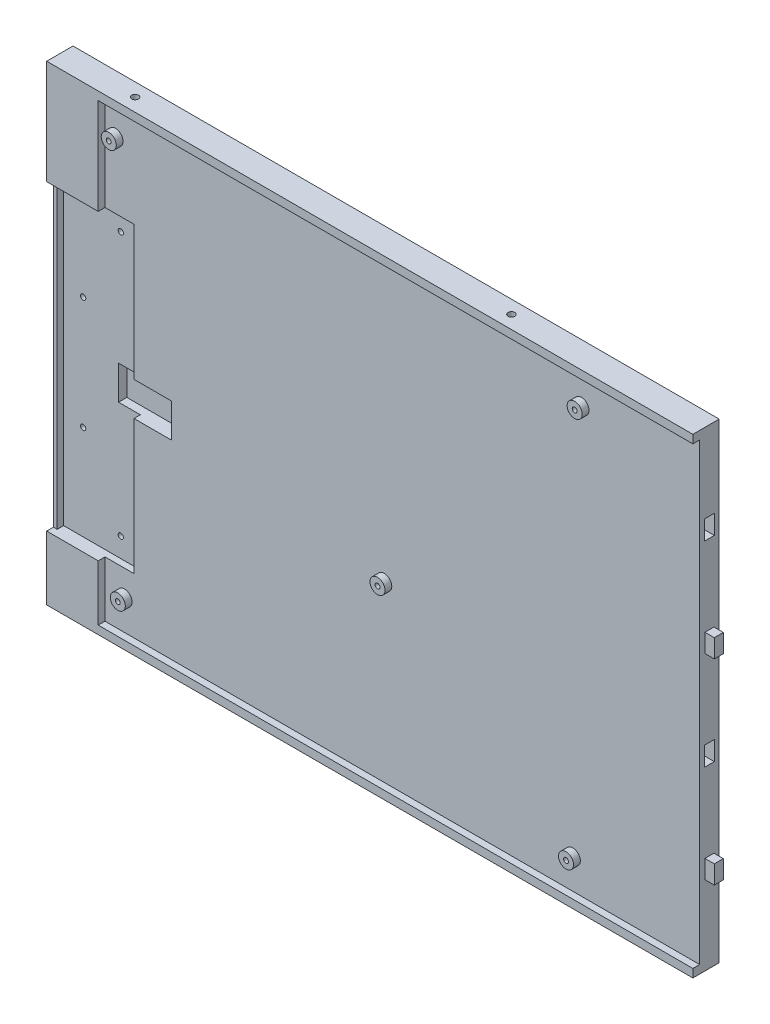
SolidWorks part; units mm, degrees
ref_plane "前视基准面" through (0, 0, 0) normal (0, 0, 1) x (1, 0, 0)
ref_plane "上视基准面" through (0, 0, 0) normal (0, 1, 0) x (1, 0, 0)
ref_plane "右视基准面" through (0, 0, 0) normal (1, 0, 0) x (0, 0, -1)
other "Configuration Table"
sketch "草图1" plane through (0, 0, 0) normal (0, 0, 1) x (1, 0, 0)
  line L1 (0, 0) -> (348.235, 0)
  line L2 (0, 0) -> (0, -124.714)
  line L3 (0, -124.714) -> (348.235, -124.714)
  line L4 (348.235, 0) -> (348.235, -124.714)
  dimension "D1" = 348.235
  dimension "D2" = 124.714
extrude "凸台-拉伸1" add sketch "草图1" along normal blind 7
sketch "草图2" plane through (0, 0, 7) normal (0, 0, 1) x (1, 0, 0)
  line L0 (348.235, 0) -> (0, 0) construction
  line L1 (2, -2) -> (346.235, -2)
  line L2 (2, -2) -> (2, -122.714)
  line L3 (2, -122.714) -> (346.235, -122.714)
  line L4 (346.235, -2) -> (346.235, -122.714)
  line L5 (348.235, -124.714) -> (348.235, 0) construction
  line L6 (0, -124.714) -> (348.235, -124.714) construction
  line L7 (0, 0) -> (0, -124.714) construction
  dimension "D1" = 2
  dimension "D2" = 2
  dimension "D3" = 2
  dimension "D4" = 2
extrude "切除-拉伸1" cut sketch "草图2" against normal blind 1.8
sketch "草图3" plane through (0, 0, 5.2) normal (0, 0, 1) x (1, 0, 0)
  circle A0 centre (4.8, -9.9) radius 2
  circle A1 centre (4.8, -9.9) radius 0.65
  circle A2 centre (7.2, -114.7) radius 2
  circle A3 centre (7.2, -114.7) radius 0.65
  circle A4 centre (76.2, -76.6) radius 2
  circle A5 centre (76.2, -76.6) radius 0.65
  circle A6 centre (128.6, -9.9) radius 2
  circle A7 centre (128.6, -9.9) radius 0.65
  circle A8 centre (126.3, -114.7) radius 2
  circle A9 centre (126.3, -114.7) radius 0.65
  circle A10 centre (185.8, -57.5) radius 2
  circle A11 centre (185.8, -57.5) radius 0.65
  circle A12 centre (252.5, -9.9) radius 2
  circle A13 centre (252.5, -9.9) radius 0.65
  circle A14 centre (245.3, -114.7) radius 2
  circle A15 centre (245.3, -114.7) radius 0.65
  circle A16 centre (333.4, -9.9) radius 2
  circle A17 centre (333.4, -9.9) radius 0.65
  circle A18 centre (333.4, -114.7) radius 2
  circle A19 centre (333.4, -114.7) radius 0.65
  circle A20 centre (266.8, -57.5) radius 2
  circle A21 centre (266.8, -57.5) radius 0.65
  dimension "D1" = 4
  dimension "D2" = 1.3
extrude "凸台-拉伸2" add sketch "草图3" along normal up to surface (1.8 mm away) up to face at (174.1175, -62.357, 7)
sketch "草图4" plane through (0, 0, 5.2) normal (0, 0, 1) x (1, 0, 0)
  line L0 (0, 0) -> (0, -124.714) construction
  line L1 (0, -27.514) -> (9.7, -27.514)
  line L2 (0, -27.514) -> (0, -107.914)
  line L3 (0, -107.914) -> (9.7, -107.914)
  line L4 (9.7, -27.514) -> (9.7, -107.914)
  line L5 (0, -124.714) -> (348.235, -124.714) construction
  dimension "D1" = 80.4
  dimension "D2" = 9.7
  dimension "D3" = 16.8
extrude "切除-拉伸2" cut sketch "草图4" against normal blind 1.7 and the other way through all contours L4 L3 L2 L1
sketch "草图6" plane through (0, 0, 5.2) normal (0, 0, 1) x (1, 0, 0)
  line L5 (3.9, -67.714) -> (9.7, -67.714) construction
  line L6 (3.9, -63.214) -> (19.7, -63.214)
  line L7 (3.9, -63.214) -> (3.9, -72.214)
  line L8 (3.9, -72.214) -> (19.7, -72.214)
  line L9 (19.7, -63.214) -> (19.7, -72.214)
  line L10 (9.7, -27.514) -> (9.7, -107.914) construction
  dimension "D1" = 9
  dimension "D2" = 5.8
  dimension "D3" = 10
extrude "切除-拉伸3" cut sketch "草图6" against normal offset from surface (3.9 mm away) 1.3 up to face at (174.1175, -62.357, 0)
sketch "草图7" plane through (0, 0, 0) normal (-1, 0, 0) x (0, 0, 1)
  line L1 (0, 0) -> (7, 0)
  line L2 (0, 0) -> (0, -27.514)
  line L3 (0, -27.514) -> (7, -27.514)
  line L4 (7, 0) -> (7, -27.514)
  line L5 (7, -107.914) -> (0, -107.914)
  line L6 (7, -107.914) -> (7, -124.714)
  line L7 (7, -124.714) -> (0, -124.714)
  line L8 (0, -107.914) -> (0, -124.714)
  line L9 (0, -107.914) -> (3.5, -107.914)
  line L10 (0, -107.914) -> (0, -27.514)
  line L11 (0, -27.514) -> (3.5, -27.514)
  line L12 (3.5, -107.914) -> (3.5, -27.514)
  line M1 (3.5, -107.914) -> (3.5, -27.514)
  line M2 (3.5, -27.514) -> (7, -27.514)
  line M3 (7, -27.514) -> (7, 0)
  line M4 (7, 0) -> (0, 0)
  line M5 (0, 0) -> (0, -124.714)
  line M6 (0, -124.714) -> (7, -124.714)
  line M7 (7, -124.714) -> (7, -107.914)
  line M8 (7, -107.914) -> (3.5, -107.914)
extrude "凸台-拉伸3" add sketch "草图7" along normal blind 11.7 contours L5 M8 M5 M6 M7 | L5 L3 M1 M5 | L3 M5 M2 M3 M4 region at (0, -13.757, 3.5) region at (0, -67.714, 1.75) region at (0, -116.314, 3.5)
sketch "草图8" plane through (0, 0, 3.5) normal (0, 0, 1) x (1, 0, 0)
  circle A0 centre (-5.5, -82.714) radius 0.7
  circle A1 centre (4.5, -102.714) radius 0.7
  circle A2 centre (-5.5, -52.714) radius 0.7
  circle A3 centre (4.5, -32.714) radius 0.7
  dimension "D1" = 1.4
extrude "切除-拉伸4" cut sketch "草图8" against normal blind 3
sketch "草图9" plane through (0, 0, 3.5) normal (0, 0, 1) x (1, 0, 0)
  line L0 (-11.7, -107.914) -> (2, -107.914) construction
  line L1 (-11.7, -27.514) -> (-10.7, -27.514)
  line L2 (-11.7, -27.514) -> (-11.7, -107.914)
  line L3 (-11.7, -107.914) -> (-10.7, -107.914)
  line L4 (-10.7, -27.514) -> (-10.7, -107.914)
  dimension "D1" = 1
extrude "凸台-拉伸4" add sketch "草图9" along normal up to surface (1.7 mm away) up to face at (64.8892, -65.9283, 5.2)
sketch "草图10" plane through (0, 0, 5.2) normal (0, 0, 1) x (1, 0, 0)
  line L1 (328.035, -30.314) -> (348.235, -30.314)
  line L2 (328.035, -30.314) -> (328.035, -110.714)
  line L3 (328.035, -110.714) -> (348.235, -110.714)
  line L4 (348.235, -30.314) -> (348.235, -110.714)
  line L6 (348.235, -124.714) -> (348.235, 0) construction
  line L9 (2, -122.714) -> (346.235, -122.714) construction
  dimension "D1" = 80.4
  dimension "D2" = 20.2
  dimension "D3" = 12
extrude "切除-拉伸5" cut sketch "草图10" against normal blind 1.7 and the other way through all
sketch "草图11" plane through (0, 0, 3.5) normal (0, 0, 1) x (1, 0, 0)
  line L0 (328.035, -70.514) -> (333.835, -70.514) construction
  line L1 (318.035, -64.764) -> (333.835, -64.764)
  line L2 (318.035, -64.764) -> (318.035, -76.264)
  line L3 (318.035, -76.264) -> (333.835, -76.264)
  line L4 (333.835, -64.764) -> (333.835, -76.264)
  line L5 (328.035, -110.714) -> (328.035, -30.314) construction
  dimension "D1" = 11.5
  dimension "D2" = 5.8
  dimension "D3" = 10
extrude "切除-拉伸6" cut sketch "草图11" against normal blind 2.2 and the other way through all
sketch "草图12" plane through (0, 0, 3.5) normal (0, 0, 1) x (1, 0, 0)
  circle A3 centre (331.235, -107.514) radius 0.65
  circle A4 centre (340.235, -86.514) radius 0.65
  circle A5 centre (340.235, -54.514) radius 0.65
  circle A6 centre (331.235, -33.514) radius 0.65
  dimension "D1" = 1.3
extrude "切除-拉伸7" cut sketch "草图12" against normal blind 3
sketch "草图13" plane through (0, 0, 0) normal (0, 0, -1) x (-1, 0, 0)
  line L0 (11.7, -124.714) -> (-348.235, -124.714) construction
  line L1 (-348.235, 0) -> (-351.235, 0)
  line L2 (-348.235, 0) -> (-348.235, -124.714)
  line L3 (-348.235, -124.714) -> (-351.235, -124.714)
  line L4 (-351.235, 0) -> (-351.235, -124.714)
  dimension "D1" = 3
extrude "凸台-拉伸5" add sketch "草图13" against normal up to surface (7 mm away) up to face at (171.1925, -14.957, 7)
sketch "草图14" plane through (0, 0, 5.2) normal (0, 0, 1) x (1, 0, 0)
  line L0 (346.235, -2) -> (2, -2) construction
  line L1 (342.435, -14) -> (348.435, -14)
  line L2 (342.435, -14) -> (342.435, -110.714)
  line L3 (342.435, -110.714) -> (348.435, -110.714)
  line L4 (348.435, -14) -> (348.435, -110.714)
  line L5 (346.235, -110.714) -> (328.035, -110.714) construction
  line L6 (351.235, 0) -> (351.235, -124.714) construction
  dimension "D1" = 12
  dimension "D2" = 6
  dimension "D3" = 2.8
extrude "切除-拉伸8" cut sketch "草图14" against normal up to surface (1.7 mm away) and the other way blind 3 up to face at (340.885, -86.514, 3.5)
sketch "草图15" plane through (351.235, 0, 0) normal (1, 0, 0) x (0, 0, -1)
  line L0 (-7, 0) -> (0, 0) construction
  line L1 (-3.5, -20) -> (-3.5, 0)
  line L2 (-3.5, -104.714) -> (-3.5, -124.714)
  line L4 (-7, -124.714) -> (0, -124.714) construction
  circle A0 centre (-3.5, -20) radius 2.6
  circle A12 centre (-3.5, -20) radius 1
  circle A13 centre (-3.5, -27.7013) radius 2.6
  circle A14 centre (-3.5, -27.7013) radius 1
  circle A15 centre (-3.5, -35.4025) radius 2.6
  circle A16 centre (-3.5, -35.4025) radius 1
  circle A17 centre (-3.5, -43.1038) radius 2.6
  circle A18 centre (-3.5, -43.1038) radius 1
  circle A19 centre (-3.5, -50.8051) radius 2.6
  circle A20 centre (-3.5, -50.8051) radius 1
  circle A21 centre (-3.5, -58.5064) radius 2.6
  circle A22 centre (-3.5, -58.5064) radius 1
  circle A23 centre (-3.5, -66.2076) radius 2.6
  circle A24 centre (-3.5, -66.2076) radius 1
  circle A25 centre (-3.5, -73.9089) radius 2.6
  circle A26 centre (-3.5, -73.9089) radius 1
  circle A27 centre (-3.5, -81.6102) radius 2.6
  circle A28 centre (-3.5, -81.6102) radius 1
  circle A29 centre (-3.5, -89.3115) radius 2.6
  circle A30 centre (-3.5, -89.3115) radius 1
  circle A31 centre (-3.5, -97.0127) radius 2.6
  circle A32 centre (-3.5, -97.0127) radius 1
  circle A33 centre (-3.5, -104.714) radius 2.6
  circle A34 centre (-3.5, -104.714) radius 1
  point P5 (-3.5, 0)
  dimension "D2" = 5.2
  dimension "D3" = 2
  dimension "D1" = 20
  dimension "D4" = 12
extrude "切除-拉伸9" cut sketch "草图15" against normal blind 0.7 contours A0 | A13 | A15 | A17 | A19 | A21 | A23 | A25 | A27 | A29 | A31
extrude "切除-拉伸10" cut sketch "草图15<3>" against normal up to surface (2.8 mm away) contours A12 | A14 | A16 | A18 | A20 | A22 | A24 | A26 | A28 | A30 | A32 up to face at (348.435, -62.357, 5.25)
sketch "草图15<3>" plane through (351.235, 0, 0) normal (1, 0, 0) x (0, 0, -1) same geometry as "草图15"
sketch "草图16" plane through (0, 0, 0) normal (0, 1, 0) x (1, 0, 0)
  line L1 (-11.7, 0) -> (351.235, 0)
  line L2 (-11.7, 0) -> (-11.7, -7)
  line L3 (-11.7, -7) -> (351.235, -7)
  line L4 (351.235, 0) -> (351.235, -7)
extrude "凸台-拉伸6" add sketch "草图16" along normal blind 0.2
sketch "草图17" plane through (0, -124.714, 0) normal (0, -1, 0) x (1, 0, 0)
  line L1 (-11.7, 7) -> (351.235, 7)
  line L2 (-11.7, 7) -> (-11.7, 0)
  line L3 (-11.7, 0) -> (351.235, 0)
  line L4 (351.235, 7) -> (351.235, 0)
extrude "凸台-拉伸7" add sketch "草图17" along normal blind 0.2
sketch "草图18" plane through (0, 0.2, 0) normal (0, 1, 0) x (1, 0, 0)
  line L0 (351.235, 0) -> (-11.7, 0) construction
  line L1 (164.5675, -0.5) -> (174.9675, -0.5)
  line L2 (164.5675, -0.5) -> (164.5675, -8.7)
  line L3 (164.5675, -8.7) -> (174.9675, -8.7)
  line L4 (174.9675, -0.5) -> (174.9675, -8.7)
  line L5 (164.5675, -0.5) -> (-11.7, -0.5) construction
  line L6 (-11.7, 0) -> (-11.7, -7) construction
  line L7 (174.9675, -0.5) -> (351.235, -0.5) construction
  line L8 (351.235, -7) -> (351.235, 0) construction
  dimension "D1" = 0.5
  dimension "D2" = 10.4
  dimension "D3" = 8.2
extrude "切除-拉伸11" cut sketch "草图18" against normal blind 1.2
sketch "草图19" plane through (0, 0.2, 0) normal (0, 1, 0) x (1, 0, 0)
  line L0 (174.9675, -7) -> (164.5675, -7) construction
  line L1 (167.6675, -2.4) -> (171.8675, -2.4)
  line L2 (167.6675, -2.4) -> (167.6675, -7)
  line L3 (167.6675, -7) -> (171.8675, -7)
  line L4 (171.8675, -2.4) -> (171.8675, -7)
  line L5 (169.7675, -2.4) -> (169.7675, 0) construction
  line L6 (351.235, 0) -> (-11.7, 0) construction
  line L7 (167.6675, -2.4) -> (-11.7, -2.4) construction
  line L8 (-11.7, 0) -> (-11.7, -7) construction
  line L9 (171.8675, -2.4) -> (351.235, -2.4) construction
  line L10 (351.235, -7) -> (351.235, 0) construction
  dimension "D1" = 2.4
  dimension "D2" = 4.2
extrude "切除-拉伸12" cut sketch "草图19" against normal up to surface (2.2 mm away) up to face at (174.1175, -2, 6.1)
sketch "草图20" plane through (0, 0.2, 0) normal (0, 1, 0) x (1, 0, 0)
  line L1 (174.7675, 0) -> (164.7675, 0)
  line L2 (174.7675, 0) -> (174.7675, -0.5)
  line L3 (174.7675, -0.5) -> (164.7675, -0.5)
  line L4 (164.7675, 0) -> (164.7675, -0.5)
  line L6 (351.235, 0) -> (-11.7, 0) construction
  point P15 (169.7675, 0)
  dimension "D1" = 10
  dimension "D2" = 0.5
extrude "凸台-拉伸8" add sketch "草图20" along normal blind 0.8
sketch "草图21" plane through (0, 1, 0) normal (0, 1, 0) x (1, 0, 0)
  line L0 (164.7675, 0) -> (174.7675, 0) construction
  line L1 (166.8675, 0) -> (172.6675, 0)
  line L2 (166.8675, 0) -> (166.8675, -1.6)
  line L3 (166.8675, -1.6) -> (172.6675, -1.6)
  line L4 (172.6675, 0) -> (172.6675, -1.6)
  point P6 (169.7675, 0)
  dimension "D1" = 5.8
  dimension "D2" = 1.6
extrude "凸台-拉伸9" add sketch "草图21" along normal blind 2.2
sketch "草图22" plane through (0, 0, 5.2) normal (0, 0, 1) x (1, 0, 0)
  line L1 (167.6675, -2) -> (212.2675, -2)
  line L2 (167.6675, -2) -> (167.6675, -6)
  line L3 (167.6675, -6) -> (212.2675, -6)
  line L4 (212.2675, -2) -> (212.2675, -6)
  line L5 (212.2675, -6) -> (199.2675, -6)
  line L6 (212.2675, -6) -> (212.2675, -19)
  line L7 (212.2675, -19) -> (199.2675, -19)
  line L8 (199.2675, -6) -> (199.2675, -19)
  line M20 (346.235, -2) -> (171.8675, -2)
  line M21 (171.8675, -2) -> (167.6675, -2)
  dimension "D1" = 4
  dimension "D2" = 44.6
  dimension "D3" = 13
  dimension "D4" = 13
extrude "切除-拉伸13" cut sketch "草图22" against normal up to surface (2.8 mm away) contours L4 L2 L3 M20 M21 | L3 L8 L7 L6 region at (189.9675, -4, 5.2) region at (205.7675, -12.5, 5.2) up to face at (169.7675, -1.5, 2.4)
sketch "草图23" plane through (0, 0, 0) normal (0, 0, -1) x (-1, 0, 0)
  line L0 (-351.235, 0.2) -> (-351.235, -124.914) construction
  line L1 (11.7, 0.2) -> (11.7, -124.914) construction
  line L2 (-351.235, 0.2) -> (-174.7675, 0.2) construction
  line L3 (11.7, -124.914) -> (-351.235, -124.914) construction
  circle A0 centre (-331.235, -19.8) radius 5.6
  circle A1 centre (-231.235, -19.8) radius 5.6
  circle A2 centre (-108.3, -19.8) radius 5.6
  circle A3 centre (-8.3, -19.8) radius 5.6
  circle A4 centre (-331.235, -104.914) radius 4.1
  circle A5 centre (-231.235, -104.914) radius 4.1
  circle A6 centre (-108.3, -104.914) radius 4.1
  circle A7 centre (-8.3, -104.914) radius 4.1
  dimension "D1" = 11.2
  dimension "D2" = 8.2
  dimension "D3" = 20
  dimension "D4" = 20
  dimension "D5" = 20
  dimension "D6" = 100
  dimension "D7" = 100
  dimension "D8" = 20
extrude "切除-拉伸14" cut sketch "草图23" against normal blind 1
sketch "草图24" plane through (0, 0.2, 0) normal (0, 1, 0) x (1, 0, 0)
  circle A0 centre (8.3, -3.5) radius 0.9
  circle A1 centre (108.3, -3.5) radius 0.9
  circle A2 centre (231.235, -3.5) radius 0.9
  circle A3 centre (331.235, -3.5) radius 0.9
  dimension "D1" = 1.8
sketch "草图25" plane through (0, 0, 5.2) normal (0, 0, 1) x (1, 0, 0)
  line L1 (-15.4741, 41.6365) -> (160, 41.6365)
  line L2 (-15.4741, 41.6365) -> (-15.4741, -143.708)
  line L3 (-15.4741, -143.708) -> (160, -143.708)
  line L4 (160, 41.6365) -> (160, -143.708)
  dimension "D1" = 160
extrude "切除-拉伸15" cut sketch "草图24" against normal blind 3
extrude "切除-拉伸16" cut sketch "草图24<2>" along normal blind 3 from surface starting at face at (169.7675, -124.914, 3.5)
sketch "草图24<2>" plane through (0, 0.2, 0) normal (0, 1, 0) x (1, 0, 0) same geometry as "草图24"
extrude "左右分割" cut sketch "草图25" against normal through all both and the other way through all flip side to cut
sketch "草图26" plane through (160, 0, 0) normal (1, 0, 0) x (0, 0, -1)
  line L0 (-2.6, -20.8228) -> (-2.6, 0.2) construction
  line L1 (-3.9, -20.8228) -> (-1.3, -20.8228)
  line L2 (-3.9, -20.8228) -> (-3.9, -25.9228)
  line L3 (-3.9, -25.9228) -> (-1.3, -25.9228)
  line L4 (-1.3, -20.8228) -> (-1.3, -25.9228)
  line L5 (-3.8, -46.9456) -> (-1.4, -46.9456)
  line L6 (-3.8, -46.9456) -> (-3.8, -51.8456)
  line L7 (-3.8, -51.8456) -> (-1.4, -51.8456)
  line L8 (-1.4, -46.9456) -> (-1.4, -51.8456)
  line L9 (-3.9, -72.8684) -> (-1.3, -72.8684)
  line L10 (-3.9, -72.8684) -> (-3.9, -77.9684)
  line L11 (-3.9, -77.9684) -> (-1.3, -77.9684)
  line L12 (-1.3, -72.8684) -> (-1.3, -77.9684)
  line L13 (-3.8, -98.9912) -> (-1.4, -98.9912)
  line L14 (-3.8, -98.9912) -> (-3.8, -103.8912)
  line L15 (-3.8, -103.8912) -> (-1.4, -103.8912)
  line L16 (-1.4, -98.9912) -> (-1.4, -103.8912)
  line L18 (0, -2) -> (-5.2, -2) construction
  line L20 (-2.6, -25.9228) -> (-2.6, -46.9456) construction
  line L21 (-2.6, -51.8456) -> (-2.6, -72.8684) construction
  line L22 (-2.6, -77.9684) -> (-2.6, -98.9912) construction
  line L23 (-2.6, -103.8912) -> (-2.6, -124.914) construction
  line L27 (0, -124.914) -> (0, 0.2) construction
  line L28 (-7, 0.2) -> (0, 0.2) construction
  line L30 (0, -124.914) -> (-7, -124.914) construction
  point P45 (-2.6, -2)
  dimension "D1" = 2.6
  dimension "D2" = 2.4
  dimension "D3" = 5.1
  dimension "D4" = 4.9
extrude "切除-拉伸18" cut sketch "草图26" against normal blind 3 contours L12 L9 L10 L11 | L4 L3 L2 L1 region at (160, -75.4184, 2.6)
extrude "凸台-拉伸10" add sketch "草图26<3>" along normal blind 2.5 contours L16 L13 L14 L15 | L8 L7 L6 L5 region at (160, -101.4412, 2.6)
sketch "草图26<3>" plane through (160, 0, 0) normal (1, 0, 0) x (0, 0, -1) same geometry as "草图26"
